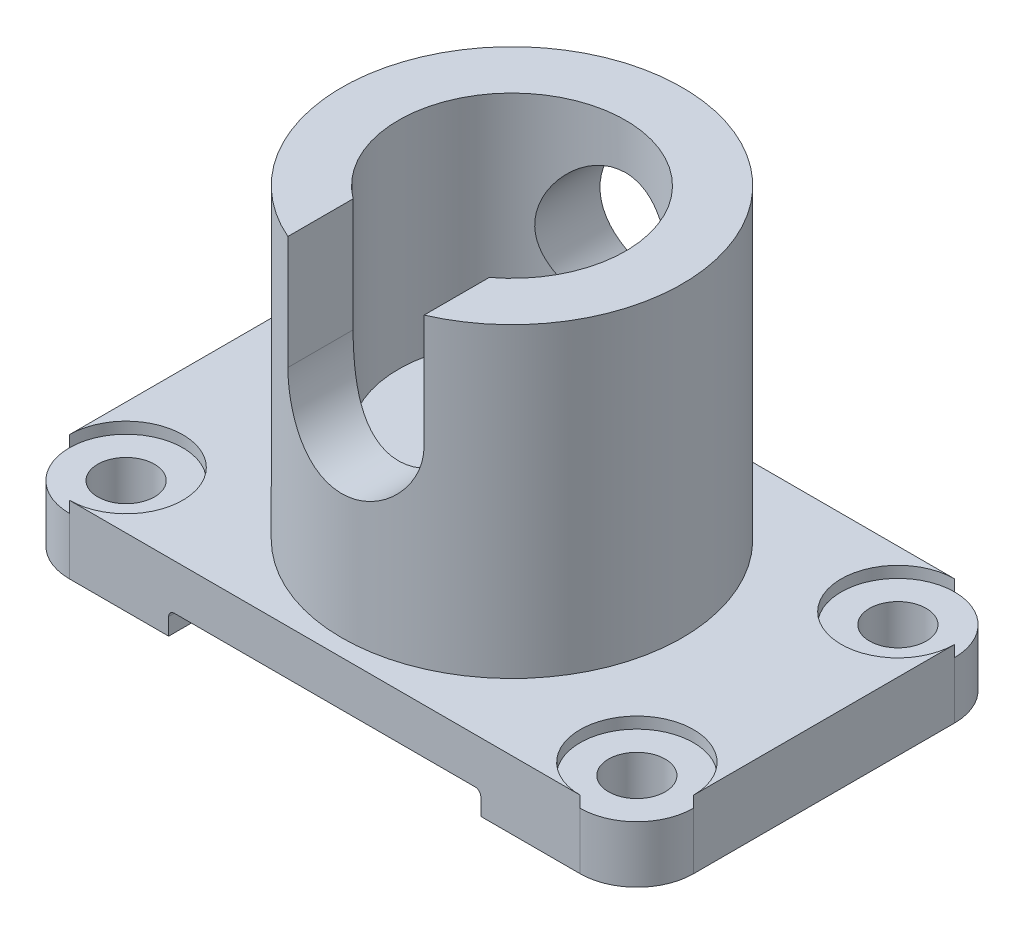
SolidWorks part; units mm, degrees
ref_plane "前视基准面" through (0, 0, 0) normal (0, 0, 1) x (1, 0, 0)
ref_plane "上视基准面" through (0, 0, 0) normal (0, 1, 0) x (1, 0, 0)
ref_plane "右视基准面" through (0, 0, 0) normal (1, 0, 0) x (0, 0, -1)
other "Configuration Table"
sketch "草图1" plane through (0, 0, 0) normal (0, 1, 0) x (1, 0, 0)
  line L1 (-45, -33) -> (45, -33)
  line L2 (-55, -23) -> (-55, 23)
  line L3 (-45, 33) -> (45, 33)
  line L4 (55, -23) -> (55, 23)
  line L5 (-55, -33) -> (55, 33) construction
  line L6 (-55, 33) -> (55, -33) construction
  arc A0 (45, -33) -> (55, -23) centre (45, -23) ccw
  arc A1 (-45, -33) -> (-55, -23) centre (-45, -23) cw
  arc A2 (-55, 23) -> (-45, 33) centre (-45, 23) cw
  arc A3 (45, 33) -> (55, 23) centre (45, 23) cw
  circle A4 centre (-45, 23) radius 5
  circle A5 centre (45, 23) radius 5
  circle A6 centre (45, -23) radius 5
  circle A7 centre (-45, -23) radius 5
  point P0 (0, 0)
  dimension "D3" = 10
  dimension "D4" = 10
  dimension "D5" = 10
  dimension "D6" = 10
  dimension "D7" = 10
  dimension "D1" = 66
  dimension "D2" = 110
extrude "凸台-拉伸1" add sketch "草图1" along normal blind 12
sketch "草图3" plane through (0, 12, 0) normal (0, 1, 0) x (1, 0, 0)
  line L4 (55, -23) -> (55, 23)
  line L5 (45, 33) -> (-45, 33)
  line L6 (-55, 23) -> (-55, -23)
  line L7 (-45, -33) -> (45, -33)
  line L8 (55, -23) -> (55, 23) construction
  line L9 (45, 33) -> (-45, 33) construction
  line L10 (-55, 23) -> (-55, -23) construction
  line L11 (-45, -33) -> (45, -33) construction
  circle A0 centre (-45, 23) radius 10
  circle A1 centre (-45, -23) radius 10
  circle A2 centre (45, -23) radius 10
  circle A3 centre (45, 23) radius 10
  arc A8 (45, -33) -> (55, -23) centre (45, -23) ccw
  arc A9 (55, 23) -> (45, 33) centre (45, 23) ccw
  arc A10 (-45, 33) -> (-55, 23) centre (-45, 23) ccw
  arc A11 (-55, -23) -> (-45, -33) centre (-45, -23) ccw
  arc A12 (45, -33) -> (55, -23) centre (45, -23) ccw construction
  arc A13 (55, 23) -> (45, 33) centre (45, 23) ccw construction
  arc A14 (-45, 33) -> (-55, 23) centre (-45, 23) ccw construction
  arc A15 (-55, -23) -> (-45, -33) centre (-45, -23) ccw construction
  point P12 (-38.5409, 16.4513)
  point P17 (-44.3221, 22.161)
  point P20 (-45.464, 23)
  point P22 (-45, 23)
  dimension "D1" = 0
extrude "切除-拉伸1" cut sketch "草图3" against normal blind 2
sketch "草图4" plane through (0, 0, 33) normal (0, 0, 1) x (1, 0, 0)
  line L0 (-27.5, 0) -> (-27.5, 3)
  line L1 (-27.5, 0) -> (27.5, 0)
  line L2 (0, 0) -> (0, 4) construction
  line L3 (-26.5, 4) -> (26.5, 4)
  line L4 (27.5, 0) -> (27.5, 3)
  arc A0 (26.5, 4) -> (27.5, 3) centre (26.5, 3) cw
  arc A1 (-27.5, 3) -> (-26.5, 4) centre (-26.5, 3) cw
  point P9 (27.5, 4)
  point P12 (-27.5, 4)
  dimension "D1" = 1
  dimension "D2" = 55
  dimension "D3" = 4
extrude "切除-拉伸2" cut sketch "草图4" against normal through all
sketch "草图5" plane through (0, 12, 0) normal (0, 1, 0) x (1, 0, 0)
  circle A0 centre (0, 0) radius 30
  circle A1 centre (0, 0) radius 20
  dimension "D1" = 60
  dimension "D2" = 40
extrude "凸台-拉伸2" add sketch "草图5" along normal blind 54
sketch "草图6" plane through (0, 12, 0) normal (0, 1, 0) x (1, 0, 0)
  circle A1 centre (0, 0) radius 20
  circle A2 centre (0, 0) radius 20
  dimension "D1" = 0
extrude "凸台-拉伸3" add sketch "草图6" along normal blind 16
sketch "草图7" plane through (0, 28, 0) normal (0, 1, 0) x (1, 0, 0)
  line L0 (5, 2) -> (5, -8)
  line L1 (-10, 10) -> (10, 10)
  line L2 (-10, 10) -> (-10, 2)
  line L3 (-10, 2) -> (-5, 2)
  line L4 (0, 10) -> (0, 4.9604) construction
  line L6 (0, 4.9604) -> (0, -8) construction
  line L8 (-5, 2) -> (-5, -8)
  line L9 (10, 10) -> (10, 2)
  line L10 (5, 2) -> (10, 2)
  circle A0 centre (0, -8) radius 5
  dimension "D1" = 20
  dimension "D3" = 10
  dimension "D2" = 8
  dimension "D4" = 10
  dimension "D5" = 10
extrude "切除-拉伸4" cut sketch "草图7" against normal blind 8 contours A0 L0 L10 L9 L1 L2 L3 L8 region at (0, 28, -4.0358)
extrude "切除-拉伸5" cut sketch "草图7<3>" against normal through all contours A0
sketch "草图7<3>" plane through (0, 28, 0) normal (0, 1, 0) x (1, 0, 0) same geometry as "草图7"
sketch "草图8" plane through (0, 0, 0) normal (0, 0, 1) x (1, 0, 0)
  line L0 (27.5, 0) -> (45, 0) construction
  circle A0 centre (0, 46) radius 12
  dimension "D1" = 24
  dimension "D2" = 46
extrude "切除-拉伸6" cut sketch "草图8" against normal through all both and the other way through all
sketch "草图9" plane through (0, 66, 0) normal (0, 1, 0) x (1, 0, 0)
  line L4 (-12, -16) -> (-12, -27.4955)
  line L6 (12, -16) -> (12, -27.4955)
  circle A0 centre (0, 0) radius 20 construction
  circle A1 centre (0, 0) radius 30
  arc A2 (-12, -27.4955) -> (12, -27.4955) centre (0, 0) ccw
  arc A3 (-12, -16) -> (12, -16) centre (0, 0) ccw
  dimension "D2" = 0
extrude "切除-拉伸7" cut sketch "草图9" against normal up to next and the other way through all
